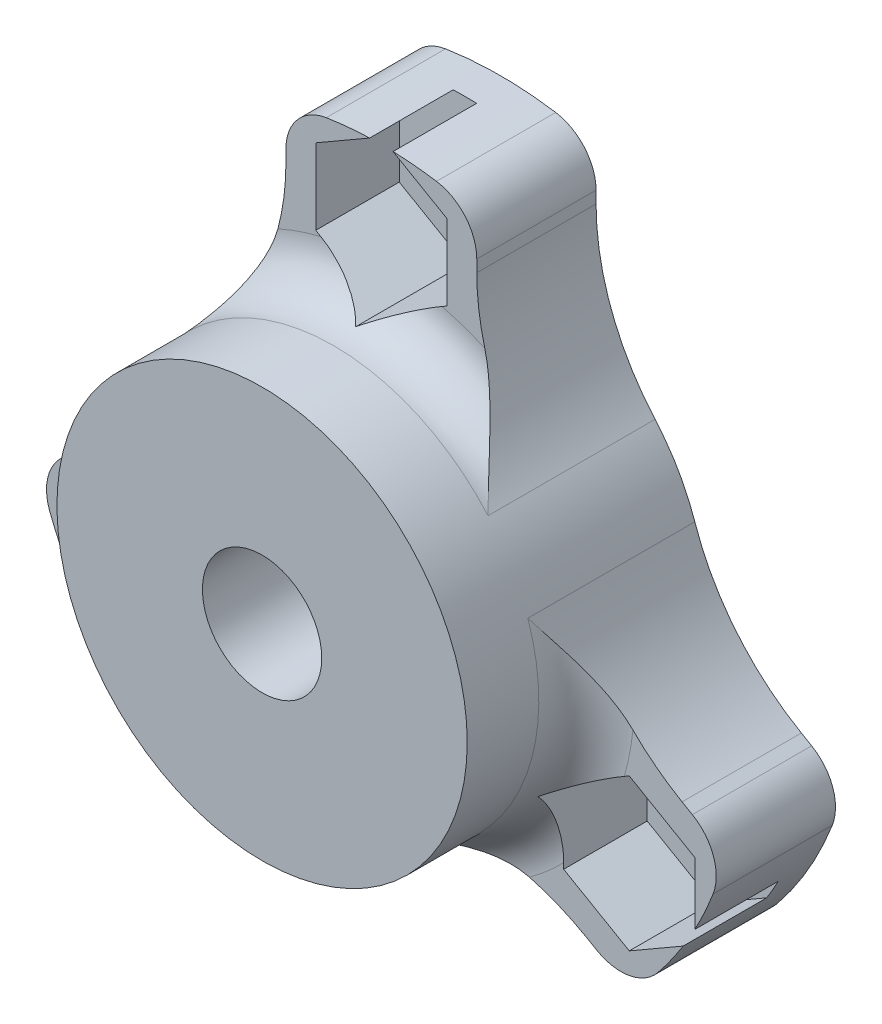
SolidWorks part; units mm, degrees
ref_plane "Front Plane" through (0, 0, 0) normal (0, 0, 1) x (1, 0, 0)
ref_plane "Top Plane" through (0, 0, 0) normal (0, 1, 0) x (1, 0, 0)
ref_plane "Right Plane" through (0, 0, 0) normal (1, 0, 0) x (0, 0, -1)
sketch "Sketch1" plane through (0, 0, 0) normal (0, 0, 1) x (1, 0, 0)
  circle A0 centre (0, 0) radius 14.9
  circle A1 centre (0, 12) radius 1.6
  circle A2 centre (10.3923, -6) radius 1.6
  circle A3 centre (-10.3923, -6) radius 1.6
  circle A4 centre (0, 0) radius 2.5
  point P11 (0, 0)
  dimension "D1" = 3
extrude "Boss-Extrude1" add sketch "Sketch1" along normal blind 5
sketch "Sketch2" plane through (0, 0, 5) normal (0, 0, 1) x (1, 0, 0)
  line L0 (13.1423, -7.5877) -> (13.1423, -4.4123)
  line L7 (0, 15.1754) -> (-2.75, 13.5877)
  line L8 (-2.75, 13.5877) -> (-2.75, 10.4123)
  line L9 (-2.75, 10.4123) -> (0, 8.8246)
  line L10 (0, 8.8246) -> (2.75, 10.4123)
  line L11 (2.75, 10.4123) -> (2.75, 13.5877)
  line L12 (2.75, 13.5877) -> (0, 15.1754)
  line L13 (13.1423, -4.4123) -> (10.3923, -2.8246)
  line L14 (10.3923, -2.8246) -> (7.6423, -4.4123)
  line L15 (7.6423, -4.4123) -> (7.6423, -7.5877)
  line L16 (7.6423, -7.5877) -> (10.3923, -9.1754)
  line L17 (10.3923, -9.1754) -> (13.1423, -7.5877)
  line L18 (-13.1423, -7.5877) -> (-10.3923, -9.1754)
  line L19 (-10.3923, -9.1754) -> (-7.6423, -7.5877)
  line L20 (-7.6423, -7.5877) -> (-7.6423, -4.4123)
  line L21 (-7.6423, -4.4123) -> (-10.3923, -2.8246)
  line L22 (-10.3923, -2.8246) -> (-13.1423, -4.4123)
  line L23 (-13.1423, -4.4123) -> (-13.1423, -7.5877)
  circle A0 centre (0, 12) radius 2.75 construction
  circle A1 centre (10.3923, -6) radius 2.75 construction
  circle A2 centre (-10.3923, -6) radius 2.75 construction
  point P27 (0, 0)
  dimension "D1" = 3
extrude "Cut-Extrude1" cut sketch "Sketch2" against normal blind 3.5
sketch "Sketch3" plane through (0, 0, 5) normal (0, 0, 1) x (1, 0, 0)
  circle A0 centre (0, 0) radius 8.6
  circle A1 centre (0, 0) radius 2.5
extrude "Boss-Extrude2" add sketch "Sketch3" along normal blind 5
sketch "Sketch5" plane through (0, 0, 5) normal (0, 0, 1) x (1, 0, 0)
  line L7 (-8.5932, -0.3425) -> (-14.4301, -3.7124)
  line L8 (-4.5932, -7.2707) -> (-10.9038, -10.9141)
  line L9 (4.5932, -7.2707) -> (10.4301, -10.6406)
  line L10 (8.5932, -0.3425) -> (14.4301, -3.7124)
  line L11 (4, 7.6131) -> (4, 14.353)
  line L14 (-4, 7.6131) -> (-4, 14.353)
  arc A0 (-4.5932, -7.2707) -> (4.5932, -7.2707) centre (0, 0) ccw
  arc A1 (-4, 14.353) -> (-14.4301, -3.7124) centre (0, 0) ccw
  arc A2 (-4, 7.6131) -> (-8.5932, -0.3425) centre (0, 0) ccw
  arc A3 (-4, 7.6131) -> (-8.5932, -0.3425) centre (0, 0) ccw
  arc A4 (-4, 7.6131) -> (-8.5932, -0.3425) centre (0, 0) ccw
  arc A5 (14.4301, -3.7124) -> (4, 14.353) centre (0, 0) ccw
  arc A6 (8.5932, -0.3425) -> (4, 7.6131) centre (0, 0) ccw
  arc A7 (8.5932, -0.3425) -> (4, 7.6131) centre (0, 0) ccw
  arc A8 (8.5932, -0.3425) -> (4, 7.6131) centre (0, 0) ccw
  arc A9 (-10.4301, -10.6406) -> (10.4301, -10.6406) centre (0, 0) ccw
  arc A10 (-4.5932, -7.2707) -> (4.5932, -7.2707) centre (0, 0) ccw
  arc A11 (-4.5932, -7.2707) -> (4.5932, -7.2707) centre (0, 0) ccw
  point P24 (0, 0)
  arc M10 (-0.4911, 14.8919) -> (-13.1423, -7.0207) centre (0, 0) ccw
  arc M17 (-12.6512, -7.8712) -> (12.6512, -7.8712) centre (0, 0) ccw
  arc M24 (13.1423, -7.0207) -> (0.4911, 14.8919) centre (0, 0) ccw
  circle M25 centre (0, 0) radius 8.6
  dimension "D3" = 3
extrude "Cut-Extrude2" cut sketch "Sketch5" against normal through all contours L11 L10 M25 M24 | L14 L7 M25 M10 | L9 L8 M25 M17 region at (-9.6735, 5.585, 5) region at (0, -11.17, 5) region at (9.6735, 5.585, 5)
fillet "Fillet1" radius 10 6 edges at (4, 7.6131, 2.5) (8.5932, -0.3425, 2.5) (4.5932, -7.2707, 2.5) (-4.5932, -7.2707, 2.5) (-8.5932, -0.3425, 2.5) (-4, 7.6131, 2.5)
fillet "Fillet2" radius 2 6 edges at (-14.4301, -3.7124, 2.5) (-10.4301, -10.6406, 2.5) (10.4301, -10.6406, 2.5) (14.4301, -3.7124, 2.5) (-4, 14.353, 2.5) (4, 14.353, 2.5)
fillet "Fillet3" radius 2 3 edges at (0, 8.6, 5) (7.4478, -4.3, 5) (-7.4478, -4.3, 5)
